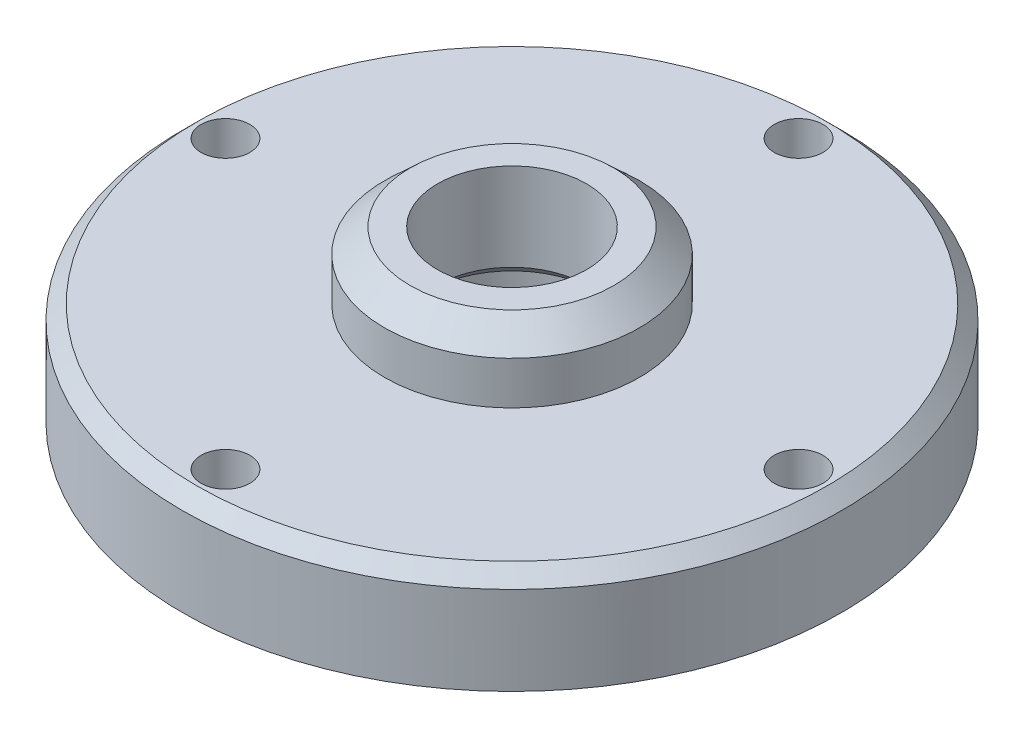
SolidWorks part; units mm, degrees
ref_plane "Front Plane" through (0, 0, 0) normal (0, 0, 1) x (1, 0, 0)
ref_plane "Top Plane" through (0, 0, 0) normal (0, 1, 0) x (1, 0, 0)
ref_plane "Right Plane" through (0, 0, 0) normal (1, 0, 0) x (0, 0, -1)
sketch "Sketch1" plane through (0, 0, 0) normal (0, 0, 1) x (1, 0, 0)
  line L0 (6.8, 0) -> (6.8, 4.953)
  line L1 (6.8, 4.953) -> (5.2, 4.953)
  line L2 (5.2, 4.953) -> (5.2, 11.829)
  line L3 (5.2, 11.829) -> (7.112, 11.829)
  line L5 (8.9, 7.1665) -> (23, 7.1665)
  line L6 (23, 7.1665) -> (23, 0)
  line L7 (23, 0) -> (6.8, 0)
  line L8 (7.112, 11.829) -> (8.9, 10.1665)
  line L9 (8.9, 10.1665) -> (8.9, 7.1665)
  line L10 (0, 0) -> (0, 16.4092) construction
  dimension "D1" = 6.8
  dimension "D2" = 23
  dimension "D3" = 4.953
  dimension "D4" = 8.9
  dimension "D5" = 11.829
  dimension "D6" = 7.1665
  dimension "D7" = 3
  dimension "D8" = 7.112
  dimension "D9" = 5.2
revolve "Revolve1" add sketch "Sketch1" angle 360 about L10
sketch "Sketch2" plane through (0, 0, 0) normal (0, 1, 0) x (1, 0, 0)
  circle A0 centre (0, 0) radius 20 construction
  point P3 (-20, 0)
  dimension "D1" = 40
hole_wizard "M3 Clearance Hole1" positions "Sketch2" profile "Sketch3" hole size "M3" standard "ANSI Metric" end condition through all
sketch "Sketch3" plane through (-20, 0, 0) normal (1, 0, 0) x (0, 0, -1)
  line L0 (0, 0) -> (0, 11.829)
  line L1 (0, 11.829) -> (1.7, 11.829)
  line L2 (1.7, 11.829) -> (1.7, 0)
  line L5 (1.7, 0) -> (0, 0)
  line L11 (0, -6.35) -> (0, 107.95) construction
  dimension "Thru Hole Dia." = 3.4
  dimension "Thru Hole Depth" = 11.829
pattern_circular "CirPattern1" count 4 over 360 about axis through (0, 0, 0) along (0, -1, 0) of "M3 Clearance Hole1"
chamfer "Chamfer1" distance 0.75 angle 45 2 edges at (0, 4.953, -5.2) (0, 0, -6.8)
chamfer "Chamfer2" distance 1 angle 45 1 edges at (0, 7.1665, -23)
